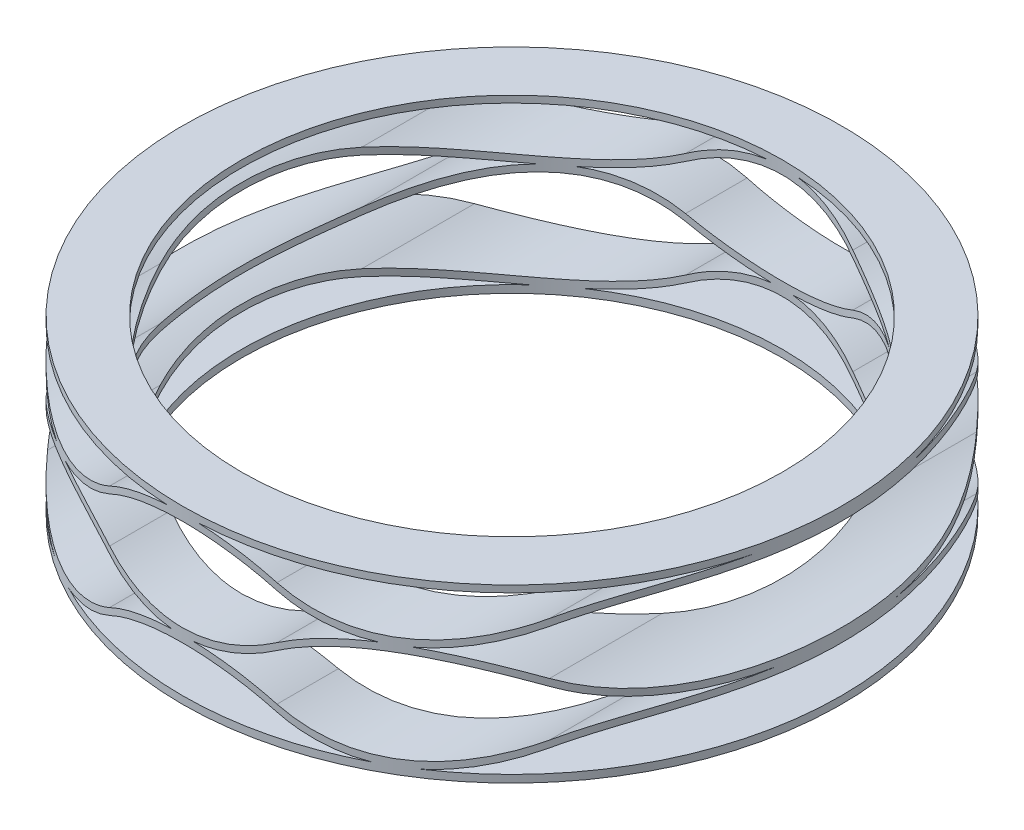
SolidWorks part; units mm, degrees
ref_plane "Front Plane" through (0, 0, 0) normal (0, 0, 1) x (1, 0, 0)
ref_plane "Top Plane" through (0, 0, 0) normal (0, 1, 0) x (1, 0, 0)
ref_plane "Right Plane" through (0, 0, 0) normal (1, 0, 0) x (0, 0, -1)
ref_plane "Plane1" through (0, 0, 0) normal (0, 1, 0) x (-1, 0, 0)
sketch "Sketch1" plane through (0, 0, 0) normal (0, 1, 0) x (-1, 0, 0)
  line L0 (14.859, -14.859) -> (14.859, 14.859)
  line L1 (14.859, 14.859) -> (-14.859, 14.859)
  line L2 (-14.859, 14.859) -> (-14.859, -14.859)
  line L3 (-14.859, -14.859) -> (14.859, -14.859)
extrude "Extrude1" add sketch "Sketch1" along normal blind 0.2794
ref_plane "Plane2" through (0, 0, 0) normal (0, 0, 1) x (1, 0, 0)
sketch "Sketch2" plane through (0, 0, 0) normal (0, 0, 1) x (1, 0, 0)
  line L0 (15.4781, 1.1007) -> (15.4781, 1.3547)
  line L1 (-15.4781, 1.3547) -> (-15.4781, 1.1007)
  arc A0 (-15.4781, 1.1007) -> (-9.2869, 1.1007) centre (-12.3825, -3.9577) cw
  arc A1 (-9.2869, 1.1007) -> (-3.0956, 1.1007) centre (-6.1913, 6.3365) ccw
  arc A2 (-3.0956, 1.1007) -> (3.0956, 1.1007) centre (0, -3.9577) cw
  arc A3 (3.0956, 1.1007) -> (9.2869, 1.1007) centre (6.1913, 6.3365) ccw
  arc A4 (9.2869, 1.1007) -> (15.4781, 1.1007) centre (12.3825, -3.9577) cw
  arc A5 (15.4781, 1.3547) -> (9.2869, 1.3547) centre (12.3825, -3.7037) ccw
  arc A6 (9.2869, 1.3547) -> (3.0956, 1.3547) centre (6.1913, 6.5905) cw
  arc A7 (3.0956, 1.3547) -> (-3.0956, 1.3547) centre (0, -3.7037) ccw
  arc A8 (-3.0956, 1.3547) -> (-9.2869, 1.3547) centre (-6.1912, 6.5905) cw
  arc A9 (-9.2869, 1.3547) -> (-15.4781, 1.3547) centre (-12.3825, -3.7037) ccw
extrude "Extrude2" add sketch "Sketch2" against normal blind 14.859 and the other way blind 14.859
ref_plane "Plane3" through (0, 0, 0) normal (0, 0, 1) x (1, 0, 0)
sketch "Sketch3" plane through (0, 0, 0) normal (0, 0, 1) x (1, 0, 0)
  line L0 (-15.4781, 3.3274) -> (-15.4781, 3.0734)
  line L1 (15.4781, 3.0734) -> (15.4781, 3.3274)
  arc A0 (-15.4781, 3.0734) -> (-9.2869, 3.0734) centre (-12.3825, 8.1317) ccw
  arc A1 (-9.2869, 3.0734) -> (-3.0956, 3.0734) centre (-6.1912, -2.1625) cw
  arc A2 (-3.0956, 3.0734) -> (3.0956, 3.0734) centre (0, 8.1317) ccw
  arc A3 (3.0956, 3.0734) -> (9.2869, 3.0734) centre (6.1913, -2.1625) cw
  arc A4 (9.2869, 3.0734) -> (15.4781, 3.0734) centre (12.3825, 8.1317) ccw
  arc A5 (15.4781, 3.3274) -> (9.2869, 3.3274) centre (12.3825, 8.3857) cw
  arc A6 (9.2869, 3.3274) -> (3.0956, 3.3274) centre (6.1913, -1.9085) ccw
  arc A7 (3.0956, 3.3274) -> (-3.0956, 3.3274) centre (0, 8.3857) cw
  arc A8 (-3.0956, 3.3274) -> (-9.2869, 3.3274) centre (-6.1913, -1.9085) ccw
  arc A9 (-9.2869, 3.3274) -> (-15.4781, 3.3274) centre (-12.3825, 8.3857) cw
extrude "Extrude3" add sketch "Sketch3" against normal blind 14.859 and the other way blind 14.859
ref_plane "Plane4" through (0, 0, 0) normal (0, 0, 1) x (1, 0, 0)
sketch "Sketch4" plane through (0, 0, 0) normal (0, 0, 1) x (1, 0, 0)
  line L0 (15.4781, 4.9953) -> (15.4781, 5.2493)
  line L1 (-15.4781, 5.2493) -> (-15.4781, 4.9953)
  arc A0 (-15.4781, 4.9953) -> (-9.2869, 4.9953) centre (-12.3825, -0.063) cw
  arc A1 (-9.2869, 4.9953) -> (-3.0956, 4.9953) centre (-6.1913, 10.2312) ccw
  arc A2 (-3.0956, 4.9953) -> (3.0956, 4.9953) centre (0, -0.063) cw
  arc A3 (3.0956, 4.9953) -> (9.2869, 4.9953) centre (6.1913, 10.2312) ccw
  arc A4 (9.2869, 4.9953) -> (15.4781, 4.9953) centre (12.3825, -0.063) cw
  arc A5 (15.4781, 5.2493) -> (9.2869, 5.2493) centre (12.3825, 0.191) ccw
  arc A6 (9.2869, 5.2493) -> (3.0956, 5.2493) centre (6.1913, 10.4852) cw
  arc A7 (3.0956, 5.2493) -> (-3.0956, 5.2493) centre (0, 0.191) ccw
  arc A8 (-3.0956, 5.2493) -> (-9.2869, 5.2493) centre (-6.1913, 10.4852) cw
  arc A9 (-9.2869, 5.2493) -> (-15.4781, 5.2493) centre (-12.3825, 0.191) ccw
extrude "Extrude4" add sketch "Sketch4" against normal blind 14.859 and the other way blind 14.859
ref_plane "Plane5" through (0, 6.096, 0) normal (0, 1, 0) x (-1, 0, 0)
sketch "Sketch5" plane through (0, 6.096, 0) normal (0, 1, 0) x (-1, 0, 0)
  line L0 (14.859, -14.859) -> (14.859, 14.859)
  line L1 (14.859, 14.859) -> (-14.859, 14.859)
  line L2 (-14.859, 14.859) -> (-14.859, -14.859)
  line L3 (-14.859, -14.859) -> (14.859, -14.859)
extrude "Extrude5" add sketch "Sketch5" along normal blind 0.254
ref_plane "Plane6" through (0, 0, 0) normal (0, 1, 0) x (-1, 0, 0)
sketch "Sketch6" plane through (0, 0, 0) normal (0, 1, 0) x (-1, 0, 0)
  line L0 (24.765, -24.765) -> (24.765, 24.765)
  line L1 (24.765, 24.765) -> (-24.765, 24.765)
  line L2 (-24.765, 24.765) -> (-24.765, -24.765)
  line L3 (-24.765, -24.765) -> (24.765, -24.765)
  circle A0 centre (0, 0) radius 12.192
  dimension "D1" = 24.384
extrude "Extrude6" cut sketch "Sketch6" along normal blind 6.35
ref_plane "Plane7" through (0, 0, 0) normal (0, 1, 0) x (-1, 0, 0)
sketch "Sketch7" plane through (0, 0, 0) normal (0, 1, 0) x (-1, 0, 0)
  circle A0 centre (0, 0) radius 10.0076
  circle A1 centre (0, 0) radius 12.192 construction
  dimension "D1" = 2.1844
extrude "Extrude7" cut sketch "Sketch7" along normal blind 6.35
